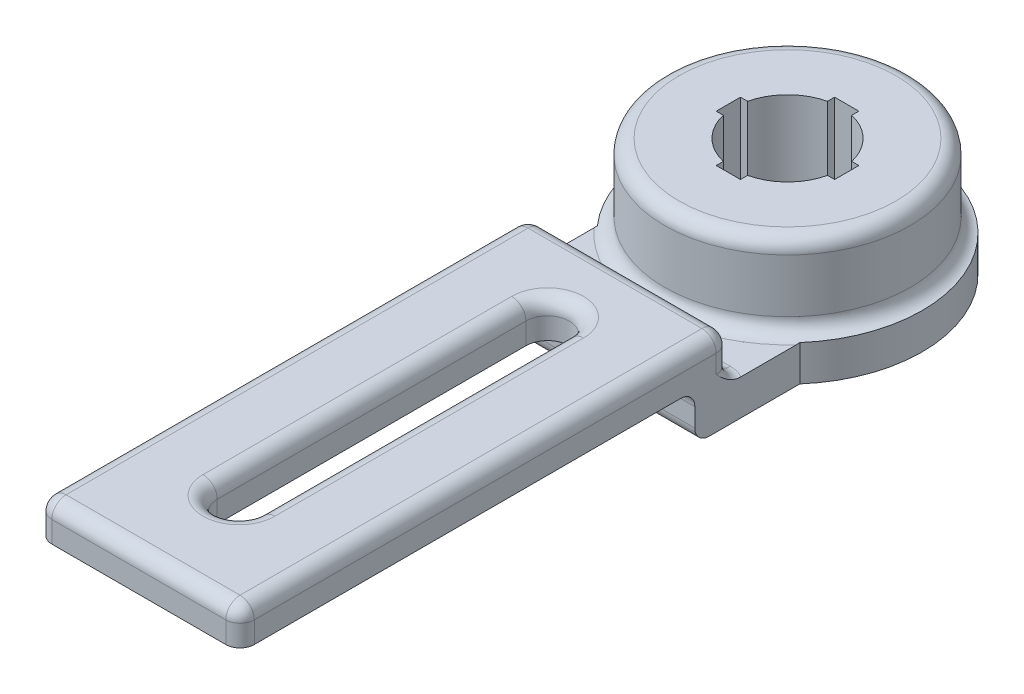
SolidWorks part; units mm, degrees
ref_plane "Alzado" through (0, 0, 0) normal (0, 0, 1) x (1, 0, 0)
ref_plane "Planta" through (0, 0, 0) normal (0, 1, 0) x (1, 0, 0)
ref_plane "Vista lateral" through (0, 0, 0) normal (1, 0, 0) x (0, 0, -1)
sketch "Croquis1" plane through (0, 0, 0) normal (1, 0, 0) x (0, 0, -1)
  line L0 (-37.8358, 7.1514) -> (30.9642, 7.1514)
  line L1 (30.9642, 7.1514) -> (30.9642, 0.5514)
  line L2 (30.9642, 0.5514) -> (40.9642, 0.5514)
  line L3 (40.9642, 0.5514) -> (40.9642, -4.4486)
  line L4 (40.9642, -4.4486) -> (25.9642, -4.4486)
  line L5 (25.9642, -4.4486) -> (25.9642, 2.1514)
  line L6 (25.9642, 2.1514) -> (-37.8358, 2.1514)
  line L7 (-37.8358, 2.1514) -> (-37.8358, 7.1514)
  dimension "D1" = 68.8
  dimension "D2" = 63.8
  dimension "D3" = 5
  dimension "D4" = 5
  dimension "D5" = 15
  dimension "D6" = 6.6
  dimension "D7" = 6.6
extrude "Saliente-Extruir1" add sketch "Croquis1" against normal blind 28.4
sketch "Croquis2" plane through (0, 7.1514, 0) normal (0, 1, 0) x (1, 0, 0)
  line L0 (-14.2, 30.9642) -> (-14.2, -37.8358) construction
  line L1 (-28.4, 30.9642) -> (0, 30.9642) construction
  line L2 (-28.4, -37.8358) -> (0, -37.8358) construction
  line L3 (-14.2, 19.5142) -> (-14.2, -23.7858) construction
  line L4 (-11.15, 19.5142) -> (-11.15, -23.7858)
  line L5 (-17.25, 19.5142) -> (-17.25, -23.7858)
  arc A0 (-11.15, 19.5142) -> (-17.25, 19.5142) centre (-14.2, 19.5142) ccw
  arc A1 (-17.25, -23.7858) -> (-11.15, -23.7858) centre (-14.2, -23.7858) ccw
  point P8 (-14.2, -2.1358)
  point P13 (-14.2, -26.8358)
  dimension "D1" = 6.1
  dimension "D2" = 43.3
  dimension "D3" = 11
extrude "Cortar-Extruir1" cut sketch "Croquis2" against normal blind 28.4
fillet "Redondeo1" radius 2 4 edges at (-14.2, 7.1514, -22.5642) (-11.15, 7.1514, 2.1358) (-14.2, 7.1514, 26.8358) (-17.25, 7.1514, 2.1358)
fillet "Redondeo2" radius 2 3 edges at (-28.4, 7.1514, 3.4358) (-14.2, 7.1514, 37.8358) (0, 7.1514, 3.4358)
fillet "Redondeo3" radius 2 4 edges at (-27.8142, 6.5656, 37.25) (-0.5858, 6.5656, 37.25) (-28.4, 3.6514, 37.8358) (0, 3.6514, 37.8358)
sketch "Croquis3" plane through (0, 2.1514, 0) normal (0, -1, 0) x (1, 0, 0)
  line L0 (-14.2, 37.8358) -> (-14.2, -25.9642) construction
  line L1 (-26.4, 37.8358) -> (-2, 37.8358) construction
  line L2 (-28.4, -25.9642) -> (0, -25.9642) construction
  line L3 (-22.82, 23.7858) -> (-22.82, 7.2858) construction
  line L4 (-20.3047, 23.7858) -> (-20.3047, 7.2858)
  line L5 (-25.3353, 23.7858) -> (-25.3353, 7.2858)
  line L6 (-22.82, -3.0142) -> (-22.82, -19.5142) construction
  line L7 (-20.3047, -3.0142) -> (-20.3047, -19.5142)
  line L8 (-25.3353, -3.0142) -> (-25.3353, -19.5142)
  line L9 (-5.58, 23.7858) -> (-5.58, 7.2858) construction
  line L10 (-28.4, 35.8358) -> (-28.4, -25.9642) construction
  line L11 (-17.25, 23.7858) -> (-17.25, -19.5142) construction
  line L13 (-8.0953, 23.7858) -> (-8.0953, 7.2858)
  line L14 (-3.0647, 23.7858) -> (-3.0647, 7.2858)
  line L15 (-5.58, -3.0142) -> (-5.58, -19.5142) construction
  line L16 (-8.0953, -3.0142) -> (-8.0953, -19.5142)
  line L17 (-3.0647, -3.0142) -> (-3.0647, -19.5142)
  arc A0 (-20.3047, 23.7858) -> (-25.3353, 23.7858) centre (-22.82, 23.7858) ccw
  arc A1 (-25.3353, 7.2858) -> (-20.3047, 7.2858) centre (-22.82, 7.2858) ccw
  arc A2 (-20.3047, -3.0142) -> (-25.3353, -3.0142) centre (-22.82, -3.0142) ccw
  arc A3 (-25.3353, -19.5142) -> (-20.3047, -19.5142) centre (-22.82, -19.5142) ccw
  arc A6 (-8.0953, 23.7858) -> (-3.0647, 23.7858) centre (-5.58, 23.7858) cw
  arc A7 (-3.0647, 7.2858) -> (-8.0953, 7.2858) centre (-5.58, 7.2858) cw
  arc A8 (-8.0953, -3.0142) -> (-3.0647, -3.0142) centre (-5.58, -3.0142) cw
  arc A9 (-3.0647, -19.5142) -> (-8.0953, -19.5142) centre (-5.58, -19.5142) cw
  point P8 (-22.82, 15.5358)
  point P13 (-22.82, -11.2642)
  point P27 (-14.2, -19.5142)
  point P29 (-5.58, 15.5358)
  point P34 (-14.2, 23.7858)
  point P41 (-5.58, -11.2642)
  dimension "D5" = 2.5153
  dimension "D1" = 16.5
  dimension "D2" = 16.5
  dimension "D3" = 5.58
  dimension "D4" = 3.0547
extrude "Cortar-Extruir2" cut sketch "Croquis3" against normal blind 3
fillet "Redondeo4" radius 2 5 edges at (-28.4, 2.8514, -30.9642) (-27.8142, 6.5656, -30.9642) (0, 2.8514, -30.9642) (-0.5858, 6.5656, -30.9642) (-14.2, 7.1514, -30.9642)
fillet "Redondeo5" radius 2 3 edges at (-27.8142, 0.5514, -30.3785) (-0.5858, 0.5514, -30.3785) (-14.2, 0.5514, -30.9642)
fillet "Redondeo6" radius 2 2 edges at (-14.2, 2.1514, -25.9642) (-14.2, -4.4486, -25.9642)
sketch "Croquis4" plane through (0, 2.1514, 0) normal (0, -1, 0) x (1, 0, 0)
  line L0 (-21.8, 32.3158) -> (-6.6, 32.3158) construction
  line L1 (-21.8, 34.8358) -> (-6.6, 34.8358)
  line L2 (-21.8, 29.7958) -> (-6.6, 29.7958)
  line L3 (-14.2, 37.8358) -> (-14.2, -25.9642) construction
  line L4 (-26.4, 37.8358) -> (-2, 37.8358) construction
  line L5 (0, -25.9642) -> (-28.4, -25.9642) construction
  line L6 (0, 35.8358) -> (0, -23.9642) construction
  arc A0 (-21.8, 34.8358) -> (-21.8, 29.7958) centre (-21.8, 32.3158) ccw
  arc A1 (-6.6, 29.7958) -> (-6.6, 34.8358) centre (-6.6, 32.3158) ccw
  point P2 (-14.2, 32.3158)
  dimension "D2" = 2.52
  dimension "D1" = 15.2
  dimension "D3" = 6.6
  dimension "D4" = 3
extrude "Cortar-Extruir3" cut sketch "Croquis4" against normal blind 3
sketch "Croquis6" plane through (0, 0.5514, 0) normal (0, 1, 0) x (1, 0, 0)
  line L1 (-28.4, 40.9642) -> (0, 40.9642) construction
  line L2 (-14.2, 53.1692) -> (-14.2, 40.9642) construction
  line L3 (-26.4, 32.9642) -> (-2, 32.9642) construction
  circle A0 centre (-14.2, 53.1692) radius 18.9
  point P3 (-14.2, 40.9642)
  dimension "D1" = 37.8
  dimension "D2" = 20.205
sketch "Croquis7" plane through (0, 0.5514, 0) normal (0, 1, 0) x (1, 0, 0)
extrude "Saliente-Extruir3" add sketch "Croquis6" against normal blind 5
sketch "Croquis9" plane through (0, 0.5514, 0) normal (0, 1, 0) x (1, 0, 0)
  line L0 (-33.1, 53.1692) -> (4.7, 53.1692) construction
  line L1 (-14.2, 72.0692) -> (-14.2, 53.1692) construction
  arc A0 (0, 40.6964) -> (-28.4, 40.6964) centre (-14.2, 53.1692) ccw construction
  circle A1 centre (-14.2, 53.1692) radius 7
  dimension "D1" = 14
extrude "Cortar-Extruir4" cut sketch "Croquis9" against normal blind 9
sketch "Croquis11" plane through (0, 0.5514, 0) normal (0, 1, 0) x (1, 0, 0)
  circle A0 centre (-14.2, 53.1692) radius 17.225
  arc A1 (0, 40.6964) -> (-28.4, 40.6964) centre (-14.2, 53.1692) ccw construction
  circle A2 centre (-14.2, 53.1692) radius 7
  circle A3 centre (-14.2, 53.1692) radius 7 construction
  dimension "D1" = 34.45
extrude "Saliente-Extruir4" add sketch "Croquis11" along normal blind 11.5
sketch "Croquis13" plane through (0, 12.0514, 0) normal (0, 1, 0) x (1, 0, 0)
  line L0 (-14.2, 60.6692) -> (-14.2, 45.6692) construction
  line L1 (-21.7, 53.1692) -> (-6.7, 53.1692) construction
  line L2 (-15.9, 60.474) -> (-15.9, 61.474)
  line L3 (-15.9, 61.474) -> (-12.5, 61.474)
  line L4 (-12.5, 61.474) -> (-12.5, 60.474)
  line L5 (-12.5, 44.8644) -> (-12.5, 45.8644)
  line L6 (-15.9, 44.8644) -> (-12.5, 44.8644)
  line L7 (-15.9, 45.8644) -> (-15.9, 44.8644)
  line L8 (-22.5048, 54.8692) -> (-22.5048, 51.4692)
  line L9 (-22.5048, 51.4692) -> (-21.5048, 51.4692)
  line L10 (-22.5048, 54.8692) -> (-21.5048, 54.8692)
  line L11 (-5.8952, 51.4692) -> (-6.8952, 51.4692)
  line L12 (-5.8952, 54.8692) -> (-5.8952, 51.4692)
  line L13 (-5.8952, 54.8692) -> (-6.8952, 54.8692)
  arc A0 (-15.9, 60.474) -> (-21.5048, 54.8692) centre (-14.2, 53.1692) ccw
  arc A1 (-12.5, 45.8644) -> (-6.8952, 51.4692) centre (-14.2, 53.1692) ccw
  arc A2 (-21.5048, 51.4692) -> (-15.9, 45.8644) centre (-14.2, 53.1692) ccw
  arc A3 (-6.8952, 54.8692) -> (-12.5, 60.474) centre (-14.2, 53.1692) ccw
  dimension "D1" = 15
  dimension "D2" = 1.7
  dimension "D3" = 1.7
  dimension "D4" = 1
  dimension "D5" = 1.7
  dimension "D6" = 1.7
  dimension "D7" = 1
sketch "Croquis14" plane through (0, 12.0514, 0) normal (0, 1, 0) x (1, 0, 0)
extrude "Cortar-Extruir5" cut sketch "Croquis13" against normal blind 11.6
fillet "Redondeo8" radius 2 1 edges at (-14.2, 12.0514, -35.9442)
sketch "Croquis16" plane through (0, -4.4486, 0) normal (0, -1, 0) x (1, 0, 0)
  line L0 (-14.2, -53.1692) -> (-14.2, -72.0692) construction
  circle A0 centre (-14.2, -53.1692) radius 15.4 construction
  arc A1 (-28.4, -40.6964) -> (0, -40.6964) centre (-14.2, -53.1692) ccw construction
  circle A2 centre (-14.2, -70.0692) radius 1.5
  circle A3 centre (-14.2, -53.1692) radius 15.4 construction
  circle A4 centre (-19.4224, -69.242) radius 1.5
  circle A5 centre (-14.2, -53.1692) radius 15.4 construction
  circle A6 centre (-24.1336, -66.8416) radius 1.5
  circle A7 centre (-14.2, -53.1692) radius 15.4 construction
  circle A8 centre (-27.8724, -63.1028) radius 1.5
  circle A9 centre (-14.2, -53.1692) radius 15.4 construction
  circle A10 centre (-30.2729, -58.3916) radius 1.5
  circle A11 centre (-14.2, -53.1692) radius 15.4 construction
  circle A12 centre (-31.1, -53.1692) radius 1.5
  circle A13 centre (-14.2, -53.1692) radius 15.4 construction
  circle A14 centre (-30.2729, -47.9468) radius 1.5
  circle A15 centre (-14.2, -53.1692) radius 15.4 construction
  circle A16 centre (-27.8724, -43.2356) radius 1.5
  circle A17 centre (-14.2, -53.1692) radius 15.4 construction
  circle A18 centre (-24.1336, -39.4968) radius 1.5
  circle A19 centre (-14.2, -53.1692) radius 15.4 construction
  circle A20 centre (-19.4224, -37.0963) radius 1.5
  circle A21 centre (-14.2, -53.1692) radius 15.4 construction
  circle A22 centre (-14.2, -36.2692) radius 1.5
  circle A23 centre (-14.2, -53.1692) radius 15.4 construction
  circle A24 centre (-8.9776, -37.0963) radius 1.5
  circle A25 centre (-14.2, -53.1692) radius 15.4 construction
  circle A26 centre (-4.2664, -39.4968) radius 1.5
  circle A27 centre (-14.2, -53.1692) radius 15.4 construction
  circle A28 centre (-0.5276, -43.2356) radius 1.5
  circle A29 centre (-14.2, -53.1692) radius 15.4 construction
  circle A30 centre (1.8729, -47.9468) radius 1.5
  circle A31 centre (-14.2, -53.1692) radius 15.4 construction
  circle A32 centre (2.7, -53.1692) radius 1.5
  circle A33 centre (-14.2, -53.1692) radius 15.4 construction
  circle A34 centre (1.8729, -58.3916) radius 1.5
  circle A35 centre (-14.2, -53.1692) radius 15.4 construction
  circle A36 centre (-0.5276, -63.1028) radius 1.5
  circle A37 centre (-14.2, -53.1692) radius 15.4 construction
  circle A38 centre (-4.2664, -66.8416) radius 1.5
  circle A39 centre (-14.2, -53.1692) radius 15.4 construction
  circle A40 centre (-8.9776, -69.242) radius 1.5
  point P69 (-14.2, -53.1692)
  dimension "D1" = 3.5
  dimension "D2" = 3
  dimension "D3" = 20
sketch "Croquis17" plane through (0, -4.4486, 0) normal (0, -1, 0) x (1, 0, 0)
extrude "Cortar-Extruir6" cut sketch "Croquis16" against normal blind 1.2
fillet "Redondeo9" radius 2 1 edges at (-14.2, 0.5514, -35.9442)
